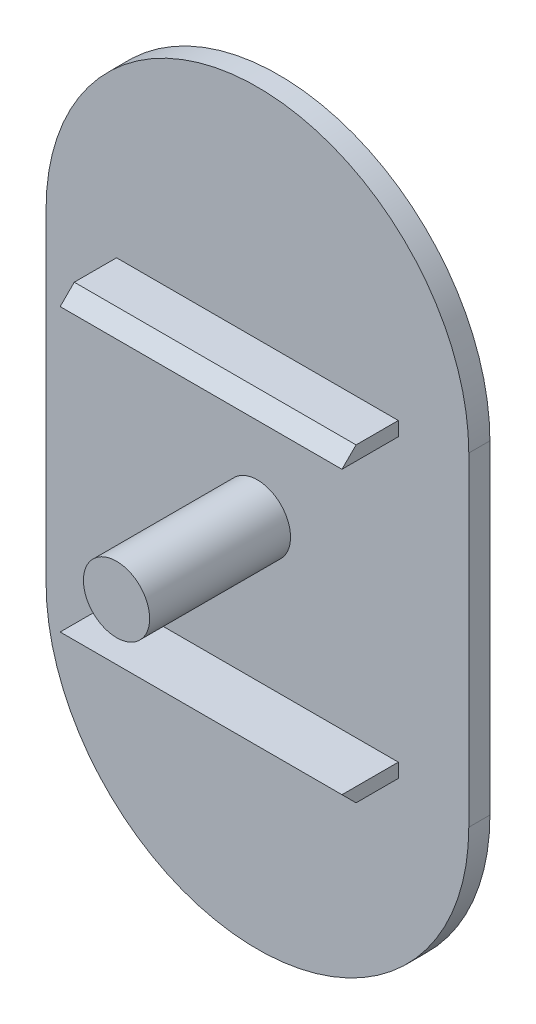
SolidWorks part; units mm, degrees
ref_plane "Płaszczyzna przednia" through (0, 0, 0) normal (0, 0, 1) x (1, 0, 0)
ref_plane "Płaszczyzna górna" through (0, 0, 0) normal (0, 1, 0) x (1, 0, 0)
ref_plane "Płaszczyzna prawa" through (0, 0, 0) normal (1, 0, 0) x (0, 0, -1)
sketch "Szkic33" plane through (0, 0, 0) normal (0, 0, 1) x (-1, 0, 0)
  line L0 (-44.5, 0) -> (45, 0) construction
  line L3 (0, 28.5) -> (0, -31.5) construction
  line L6 (-6, 12.5) -> (6, 12.5) construction
  line L9 (-6, 14.5) -> (6, 14.5)
  line L12 (-6, 10.5) -> (6, 10.5)
  line L13 (-6, -12.5) -> (6, -12.5) construction
  line L14 (-6, -14.5) -> (6, -14.5)
  line L15 (-6, -10.5) -> (6, -10.5)
  line L16 (-59.081, 0) -> (59.081, 0) construction
  circle A0 centre (0, 12.5) radius 4
  circle A4 centre (0, -12.5) radius 4
  arc A7 (-6, 14.5) -> (-6, 10.5) centre (-6, 12.5) ccw
  arc A8 (6, 10.5) -> (6, 14.5) centre (6, 12.5) ccw
  arc A9 (-6, -14.5) -> (-6, -10.5) centre (-6, -12.5) cw
  arc A10 (6, -10.5) -> (6, -14.5) centre (6, -12.5) cw
  point P14 (0, 12.5)
  point P26 (0, -12.5)
  point P34 (0, 0)
  dimension "D1" = 8
  dimension "D2" = 12.5
  dimension "D3" = 4
  dimension "D4" = 6
sketch "Szkic34" plane through (0, 0, 0) normal (0, 0, 1) x (1, 0, 0)
  line L12 (-47, 26.5) -> (-47, -26.5)
  line L13 (-43, -30.5) -> (43, -30.5)
  line L14 (47, -26.5) -> (47, 26.5)
  line L15 (43, 30.5) -> (-43, 30.5)
  spline S4 degree 3 poles (-43, 30.5) (-45.3431, 30.5) (-47, 28.8431) (-47, 26.5) knots 0 0 0 0 1 1 1 1 weights 1 0.804738 0.804738 1
  spline S5 degree 3 poles (-47, -26.5) (-47, -28.8431) (-45.3431, -30.5) (-43, -30.5) knots 0 0 0 0 1 1 1 1 weights 1 0.804738 0.804738 1
  spline S6 degree 3 poles (43, -30.5) (45.3431, -30.5) (47, -28.8431) (47, -26.5) knots 0 0 0 0 1 1 1 1 weights 1 0.804738 0.804738 1
  spline S7 degree 3 poles (47, 26.5) (47, 28.8431) (45.3431, 30.5) (43, 30.5) knots 0 0 0 0 1 1 1 1 weights 1 0.804738 0.804738 1
sketch "Szkic35" plane through (0, 0, 0) normal (0, 0, 1) x (1, 0, 0)
  line L0 (-15, -11.5) -> (-15, 11.5)
  line L1 (0, 16.5) -> (-15, 16.5) construction
  line L2 (0, 16.5) -> (15, 16.5) construction
  line L3 (22.2734, -16.5) -> (7.2734, -16.5) construction
  line L4 (22.2734, -16.5) -> (15, -16.5) construction
  line L5 (15, 11.5) -> (15, -11.5)
  line L8 (0, 26.5) -> (0, -26.5) construction
  line L9 (-15, 0) -> (15, 0) construction
  circle A0 centre (0, -12.5) radius 4 construction
  circle A1 centre (0, 12.5) radius 4 construction
  arc A2 (-15, 11.5) -> (15, 11.5) centre (0, 11.5) cw
  arc A3 (-15, -11.5) -> (15, -11.5) centre (0, -11.5) ccw
  circle A4 centre (0, 0) radius 2.5 construction
  dimension "D6" = 1
  dimension "D7" = 1
  dimension "D8" = 5
  dimension "D1" = 15
  dimension "D2" = 15
  dimension "D3" = 5
  dimension "D4" = 5
  dimension "D5" = 15
  dimension "D9" = 15
extrude "Dodanie-wyciągnięcie2" add sketch "Szkic35" along normal blind 1.5
sketch "Szkic37" plane through (0, 0, 0) normal (0, 0, -1) x (-1, 0, 0)
  circle A0 centre (0, 12.5) radius 1.85
  circle A1 centre (0, -12.5) radius 1.85
  dimension "D1" = 3.7
  dimension "D2" = 2
extrude "Dodanie-wyciągnięcie3" add sketch "Szkic37" along normal blind 1.5
sketch "Szkic38" plane through (0, 0, -1.5) normal (0, 0, -1) x (-1, 0, 0)
  circle A0 centre (0, 12.5) radius 3.85
  circle A1 centre (0, -12.5) radius 3.85
  dimension "D1" = 7.7
  dimension "D2" = 2
extrude "Dodanie-wyciągnięcie4" add sketch "Szkic38" along normal blind 1.7
fillet "Zaokrąglenie1" radius 2 2 edges at (-3.85, -12.5, -3.2) (-3.85, 12.5, -3.2)
sketch "Szkic39" plane through (0, 0, 1.5) normal (0, 0, 1) x (1, 0, 0)
  circle A0 centre (0, 0) radius 2.35
  circle A2 centre (0, 0) radius 2.5 construction
  dimension "D1" = 4.7
  dimension "D2" = 4.7
extrude "Dodanie-wyciągnięcie5" add sketch "Szkic39" along normal blind 10
sketch "Szkic40" plane through (0, 0, 1.5) normal (0, 0, 1) x (1, 0, 0)
  line L0 (-10, 10) -> (-10, 11)
  line L1 (-10, 10) -> (10, 10)
  line L2 (-10, 10) -> (-10, -10) construction
  line L3 (-10, -10) -> (10, -10)
  line L4 (10, 10) -> (10, -10) construction
  line L5 (-10, 10) -> (10, -10) construction
  line L6 (-10, -10) -> (10, 10) construction
  line L7 (-10, 11) -> (10, 11)
  line L8 (10, 11) -> (10, 10)
  line L9 (-10, -10) -> (-10, -11)
  line L10 (-10, -11) -> (10, -11)
  line L11 (10, -11) -> (10, -10)
  point P0 (0, 0)
  dimension "D1" = 20
  dimension "D2" = 20
  dimension "D3" = 1
extrude "Dodanie-wyciągnięcie6" add sketch "Szkic40" along normal blind 4
chamfer "Sfazowanie1" distance 1 angle 45 2 edges at (0, 11, 5.5) (0, -11, 5.5)
ref_plane "Płaszczyzna1" through (0, 0, 0) normal (0, -1, 0) x (-1, 0, 0)
